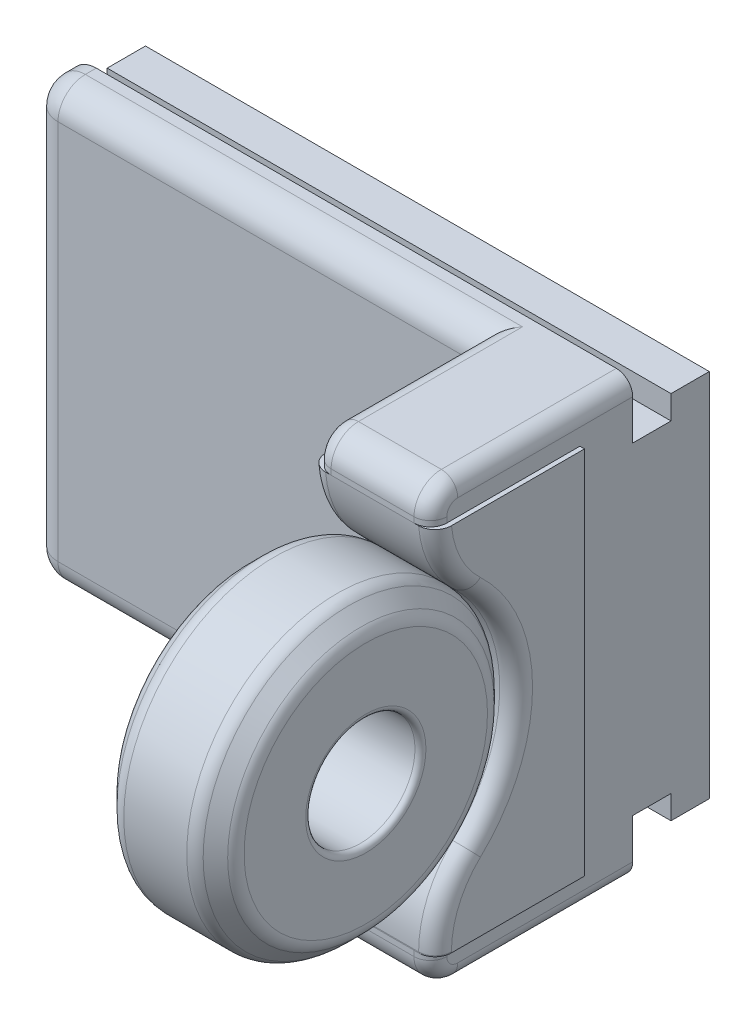
SolidWorks part; units mm, degrees
ref_plane "Ön Düzlem" through (0, 0, 0) normal (0, 0, 1) x (1, 0, 0)
ref_plane "Üst Düzlem" through (0, 0, 0) normal (0, 1, 0) x (1, 0, 0)
ref_plane "Sağ Düzlem" through (0, 0, 0) normal (1, 0, 0) x (0, 0, -1)
sketch "Çizim1" plane through (0, 0, 0) normal (0, 0, 1) x (1, 0, 0)
  line L0 (-290.891, 1.3305) -> (-290.891, -66.3305)
  line L1 (-290.891, -3) -> (-394, -3)
  line L8 (-290.891, 1.3305) -> (-394, 1.3305)
  line L9 (-394, 1.3305) -> (-394, -3)
  line L10 (-394, -3) -> (-290.891, -3)
  line L16 (-290.891, -62) -> (-394, -62)
  line L17 (-394, -62) -> (-394, -66.3305)
  line L18 (-394, -66.3305) -> (-290.891, -66.3305)
  line L24 (-394, -3) -> (-394, -62)
  line L25 (-394, -62) -> (-290.891, -62)
extrude "Yükseklik-Ekstrüzyon1" add sketch "Çizim1" along normal blind 21 contours L1 L24 L16 L0 region at (-342.4455, -32.5, 0)
extrude "Yükseklik-Ekstrüzyon2" add sketch "Çizim1<3>" along normal blind 7 contours L17 L18 L0 L16 | L8 L9 L1 L0 region at (-342.4455, -0.8347, 0) region at (-342.4455, -64.1653, 0)
sketch "Çizim1<3>" plane through (0, 0, 0) normal (0, 0, 1) x (1, 0, 0) same geometry as "Çizim1"
sketch "Çizim2" plane through (0, 0, 21) normal (0, 0, 1) x (1, 0, 0)
  line L2 (-394, 1.3305) -> (-394, -66.3305)
  line L4 (-290.891, 1.3305) -> (-290.891, -66.3305)
  line L6 (-394, 1.3305) -> (-394, 7.3305)
  line L7 (-394, 7.3305) -> (-290.891, 7.3305)
  line L8 (-290.891, 1.3305) -> (-290.891, 7.3305)
  line L10 (-394, -66.3305) -> (-394, -72.3305)
  line L11 (-394, -72.3305) -> (-290.891, -72.3305)
  line L12 (-290.891, -66.3305) -> (-290.891, -72.3305)
  dimension "D1" = 6
  dimension "D2" = 6
extrude "Yükseklik-Ekstrüzyon3" add sketch "Çizim2" against normal blind 7
sketch "Çizim3" plane through (0, 0, 21) normal (0, 0, 1) x (1, 0, 0)
  line L0 (-394, -72.3305) -> (-290.891, -72.3305) construction
  line L1 (-290.891, 7.3305) -> (-312.0497, 7.3305)
  line L2 (-290.891, 7.3305) -> (-290.891, -72.3305)
  line L3 (-290.891, -72.3305) -> (-312.0497, -72.3305)
  line L4 (-312.0497, 7.3305) -> (-312.0497, -72.3305)
extrude "Yükseklik-Ekstrüzyon4" add sketch "Çizim3" along normal blind 30
sketch "Çizim4" plane through (-312.0497, 0, 0) normal (-1, 0, 0) x (0, 0, 1)
  line L0 (51, 7.3305) -> (51, -72.3305) construction
  line L1 (51, -11.6462) -> (51, 1.3305)
  line L2 (51, 1.3305) -> (23.6587, 1.3305)
  line L3 (23.6587, 1.3305) -> (23.6587, -66.3305)
  line L4 (23.6587, -66.3305) -> (51, -66.3305)
  line L5 (51, -66.3305) -> (51, -53.3538)
  line L6 (51, -11.6462) -> (51, 1.3305)
  line L7 (51, 7.3305) -> (21, 7.3305) construction
  line L8 (51, -72.3305) -> (21, -72.3305) construction
  line L9 (51, -11.6462) -> (51, -53.3538)
  circle A1 centre (63.6587, -31.6722) radius 27.5
  line M5 (51, -72.3305) -> (51, 7.3305)
  dimension "D3" = 55
  dimension "D1" = 6
  dimension "D2" = 6
  dimension "D4" = 40
extrude "Kes-Ekstrüzyon1" cut sketch "Çizim4" against normal blind 30 contours L2 L3 L4 M5 | M5 region at (-312.0497, -31.6722, 44.9004) region at (-312.0497, -32.8212, 34.3918)
extrude "Yükseklik-Ekstrüzyon5" add sketch "Çizim4<3>" against normal blind 22 and the other way blind 1 separate body contours L2 L3 L4 M5 region at (-312.0497, -32.8212, 34.3918)
sketch "Çizim4<3>" plane through (-312.0497, 0, 0) normal (-1, 0, 0) x (0, 0, 1) same geometry as "Çizim4"
fillet "Radyus1" radius 20 2 edges at (-301.5497, -56.0855, 51) (-301.5497, -7.259, 51)
fillet "Radyus2" radius 5 2 edges at (-301.4703, 7.3305, 51) (-301.4703, -72.3305, 51)
fillet "Radyus3" radius 5 5 edges at (-353.0248, -72.3305, 21) (-353.0248, 7.3305, 21) (-394, -32.5, 21) (-394, 7.3305, 17.5) (-394, -72.3305, 17.5)
fillet "Radyus4" radius 3 12 edges at (-290.891, 1.8305, 51) (-290.891, 5.8661, 49.5355) (-290.891, -66.8305, 51) (-290.891, -70.8661, 49.5355) (-312.0497, 1.8305, 51) (-312.0497, 5.8661, 49.5355) (-312.0497, -66.8305, 51) (-312.0497, -70.8661, 49.5355) (-290.891, 7.3305, 30) (-290.891, -72.3305, 30) (-312.0497, 7.3305, 31) (-312.0497, -72.3305, 31)
fillet "Radyus5" radius 3 8 edges at (-313.0497, -5.7493, 49.1044) (-313.0497, -66.2471, 51) (-313.0497, -58.2587, 49.3714) (-290.0497, -5.7493, 49.1044) (-290.0497, -66.2471, 51) (-290.0497, -58.2587, 49.3714) (-313.0497, -31.6484, 36.1587) (-290.0497, -31.6484, 36.1587)
sketch "Çizim5" plane through (-290.0497, 0, 0) normal (1, 0, 0) x (0, 0, -1)
  circle A0 centre (-63.6587, -31.6722) radius 27.5
  circle A1 centre (-63.6587, -31.6722) radius 10
  dimension "D1" = 20
extrude "Yükseklik-Ekstrüzyon6" add sketch "Çizim5" against normal blind 22 separate body
chamfer "Pah1" distance 4 angle 45 2 edges at (-312.0497, -31.6722, 36.1587) (-290.0497, -31.6722, 36.1587)
fillet "Radyus6" radius 3 4 edges at (-312.0497, -31.6722, 40.1587) (-308.0497, -31.6722, 36.1587) (-294.0497, -31.6722, 36.1587) (-290.0497, -31.6722, 40.1587)
fillet "Radyus7" radius 1 2 edges at (-312.0497, -31.6722, 53.6587) (-290.0497, -31.6722, 53.6587)
ref_plane "Düzlem1" through (-312.0497, -67.3305, 21) normal (1, 0, 0) x (0, 0, -1)
